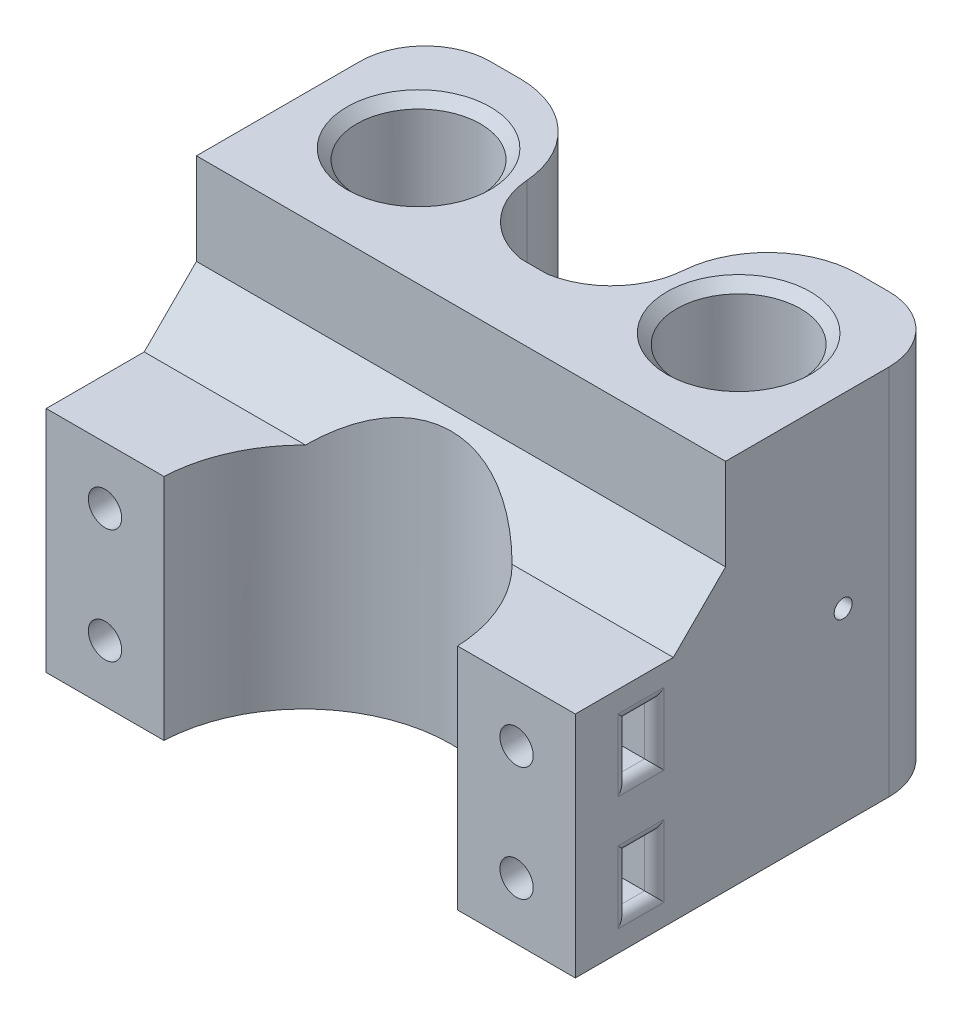
SolidWorks part; units mm, degrees
ref_plane "Alzado" through (0, 0, 0) normal (0, 0, 1) x (1, 0, 0)
ref_plane "Planta" through (0, 0, 0) normal (0, 1, 0) x (1, 0, 0)
ref_plane "Vista lateral" through (0, 0, 0) normal (1, 0, 0) x (0, 0, -1)
sketch "Croquis2" plane through (0, 0, 0) normal (0, 1, 0) x (1, 0, 0)
  line L0 (24.5, 0) -> (-24.5, 0) construction
  line L1 (40.5, 17) -> (-40.5, 17)
  line L2 (-40.5, 17) -> (-40.5, -42)
  line L3 (-40.5, -42) -> (-22.5, -42)
  line L4 (22.5, -42) -> (40.5, -42)
  line L5 (40.5, -42) -> (40.5, 17)
  circle A0 centre (-24.5, 0) radius 9.475
  circle A1 centre (24.5, 0) radius 9.475
  arc A2 (-22.5, -42) -> (22.5, -42) centre (0, -42) cw
  point P4 (0, 0)
  point P10 (0, 17)
  dimension "D1" = 18.95
  dimension "D5" = 22.5
  dimension "D2" = 49
  dimension "D3" = 17
  dimension "D4" = 16
  dimension "D6" = 59
extrude "Saliente-Extruir1" add sketch "Croquis2" along normal blind 35
sketch "Croquis3" plane through (0, 35, 0) normal (0, 1, 0) x (1, 0, 0)
  line L0 (-40.5, 17) -> (-25.923, 17)
  line L1 (40.5, 17) -> (-40.5, 17) construction
  line L3 (40.5, -18) -> (-40.5, -18)
  line L4 (-40.5, 17) -> (-40.5, -42) construction
  line L5 (-40.5, -18) -> (-40.5, 17)
  line L7 (0, 17) -> (0, -19.5) construction
  line L8 (-2, -6.8322) -> (2, -6.8322)
  line L11 (40.5, -18) -> (40.5, 17)
  line L12 (40.5, 17) -> (25.923, 17)
  arc A0 (-25.923, 17) -> (-11.9644, 4.0769) centre (-25.923, 3) cw
  circle A1 centre (0, 5) radius 11 construction
  arc A2 (-11.9644, 4.0769) -> (-2, -6.8322) centre (0, 5) ccw
  arc A4 (22.5, -42) -> (-22.5, -42) centre (0, -42) ccw construction
  circle A8 centre (24.5, 0) radius 9.475
  circle A9 centre (-24.5, 0) radius 9.475 construction
  circle A11 centre (-24.5, 0) radius 9.475
  arc A12 (11.9644, 4.0769) -> (2, -6.8322) centre (0, 5) cw
  arc A13 (25.923, 17) -> (11.9644, 4.0769) centre (25.923, 3) ccw
  point P7 (-24.5, 0)
  point P8 (24.5, 0)
  point P32 (0, -6.8322)
  point P34 (0, -18)
  dimension "D2" = 14
  dimension "D3" = 22
  dimension "D5" = 2
  dimension "D7" = 1
  dimension "D1" = 35
  dimension "D4" = 5
extrude "Saliente-Extruir2" add sketch "Croquis3" along normal blind 22
chamfer "Chaflán1" distance 8 angle 45 1 edges at (0, 35, 18)
fillet "Redondeo3" radius 10 2 edges at (-40.5, 28.5, -17) (40.5, 28.5, -17)
sketch "Croquis4" plane through (0, 57, 0) normal (0, 1, 0) x (1, 0, 0)
  line L2 (-2, -6.8322) -> (2, -6.8322)
  line L3 (25.923, 17) -> (-25.923, 17)
  line L4 (-2, -6.8322) -> (2, -6.8322)
  line L5 (25.923, 17) -> (-25.923, 17)
  arc A4 (-11.9644, 4.0769) -> (-25.923, 17) centre (-25.923, 3) ccw
  arc A5 (-11.9644, 4.0769) -> (-2, -6.8322) centre (0, 5) ccw
  arc A6 (2, -6.8322) -> (11.9644, 4.0769) centre (0, 5) ccw
  arc A7 (25.923, 17) -> (11.9644, 4.0769) centre (25.923, 3) ccw
  arc A8 (-11.9644, 4.0769) -> (-25.923, 17) centre (-25.923, 3) ccw
  arc A9 (-11.9644, 4.0769) -> (-2, -6.8322) centre (0, 5) ccw
  arc A10 (2, -6.8322) -> (11.9644, 4.0769) centre (0, 5) ccw
  arc A11 (25.923, 17) -> (11.9644, 4.0769) centre (25.923, 3) ccw
  dimension "D1" = 0
extrude "Cortar-Extruir1" cut sketch "Croquis4" against normal blind 5 from surface at -22 starting at face at (0, 35, -5.088)
chamfer "Chaflán2" distance 1.5 angle 45 4 edges at (-24.5, 0, 9.475) (24.5, 0, 9.475) (24.5, 57, -9.475) (-24.5, 57, 9.475)
sketch "Croquis5" plane through (0, 30, 0) normal (0, 1, 0) x (1, 0, 0)
  circle A0 centre (0, 5) radius 11 construction
  arc A3 (-11.9644, 4.0769) -> (-2, -6.8322) centre (0, 5) ccw construction
  circle A4 centre (0, 5) radius 5
  circle A5 centre (0, 5) radius 8 construction
  circle A6 centre (0, 13) radius 1.375
  circle A7 centre (8, 5) radius 1.375
  circle A8 centre (0, -3) radius 1.375
  circle A9 centre (-8, 5) radius 1.375
  dimension "D1" = 22
  dimension "D2" = 10
  dimension "D3" = 2.75
  dimension "D4" = 8
extrude "Cortar-Extruir2" cut sketch "Croquis5" against normal through all
chamfer "Chaflán3" distance 0.5 angle 45 10 edges at (8, 0, -3.625) (0, 0, -11.625) (-8, 0, -3.625) (0, 0, 4.375) (0, 30, -11.625) (8, 30, -3.625) (0, 30, 4.375) (-8, 30, -3.625) (0, 0, 0) (0, 30, 0)
sketch "Croquis6" plane through (0, 35, 0) normal (0, 1, 0) x (1, 0, 0)
  line L0 (40.5, -42) -> (40.5, -26) construction
  line L1 (-40.5, -42) -> (40.5, -42)
  line L2 (-40.5, -42) -> (-40.5, -41)
  line L3 (-40.5, -41) -> (40.5, -41)
  line L4 (40.5, -42) -> (40.5, -41)
  dimension "D1" = 1
extrude "Cortar-Extruir3" cut sketch "Croquis6" against normal up to next
sketch "Croquis7" plane through (40.5, 0, 0) normal (1, 0, 0) x (0, 0, -1)
  line L0 (9.475, 28.5) -> (-9.475, 28.5) construction
  line L1 (9.475, 1.5) -> (9.475, 55.5) construction
  line L2 (-9.475, 55.5) -> (-9.475, 1.5) construction
  circle A0 centre (0, 28.5) radius 1.375
  dimension "D1" = 2.75
extrude "Cortar-Extruir4" cut sketch "Croquis7" against normal up to next
mirror "Simetría1" about plane through (0, 0, 0) normal (1, 0, 0) of "Cortar-Extruir4"
sketch "Croquis8" plane through (0, 0, 41) normal (0, 0, 1) x (1, 0, 0)
  circle A0 centre (31.5, 26.25) radius 2.55
  circle A1 centre (31.5, 8.75) radius 2.55
  circle A2 centre (-31.5, 26.25) radius 2.55
  circle A3 centre (-31.5, 8.75) radius 2.55
  dimension "D1" = 5.1
extrude "Cortar-Extruir5" cut sketch "Croquis8" against normal blind 17
sketch "Croquis9" plane through (0, 0, 41) normal (0, 0, 1) x (1, 0, 0)
  line L0 (-22.4778, 35) -> (-40.5, 35) construction
  line L1 (-33.8094, 22.25) -> (-29.1906, 22.25)
  line L2 (-29.1906, 22.25) -> (-26.8812, 26.25)
  line L3 (-26.8812, 26.25) -> (-29.1906, 30.25)
  line L4 (-29.1906, 30.25) -> (-33.8094, 30.25)
  line L5 (-33.8094, 30.25) -> (-36.1188, 26.25) construction
  line L6 (-36.1188, 26.25) -> (-33.8094, 22.25) construction
  line L7 (-36.1188, 8.75) -> (-33.8094, 4.75) construction
  line L8 (-33.8094, 4.75) -> (-29.1906, 4.75)
  line L9 (-29.1906, 4.75) -> (-26.8812, 8.75)
  line L10 (-26.8812, 8.75) -> (-29.1906, 12.75)
  line L11 (-29.1906, 12.75) -> (-33.8094, 12.75)
  line L12 (-33.8094, 12.75) -> (-36.1188, 8.75) construction
  line L25 (-40.5, 22.25) -> (-33.8094, 22.25)
  line L26 (0, 0) -> (0, 41.5) construction
  line L27 (-22.4778, 0) -> (22.4778, 0) construction
  line L28 (-33.8094, 30.25) -> (-40.5, 30.25)
  line L29 (-40.5, 0) -> (-40.5, 35) construction
  line L30 (-40.5, 30.25) -> (-40.5, 22.25)
  line L32 (-33.8094, 12.75) -> (-40.5, 12.75)
  line L33 (-40.5, 12.75) -> (-40.5, 4.75)
  line L34 (-40.5, 4.75) -> (-33.8094, 4.75)
  line L35 (40.5, 12.75) -> (40.5, 4.75)
  line L36 (33.8094, 12.75) -> (40.5, 12.75)
  line L37 (29.1906, 12.75) -> (33.8094, 12.75)
  line L38 (26.8812, 8.75) -> (29.1906, 12.75)
  line L39 (29.1906, 4.75) -> (26.8812, 8.75)
  line L40 (33.8094, 4.75) -> (29.1906, 4.75)
  line L41 (40.5, 4.75) -> (33.8094, 4.75)
  line L42 (40.5, 30.25) -> (40.5, 22.25)
  line L43 (33.8094, 30.25) -> (40.5, 30.25)
  line L44 (29.1906, 30.25) -> (33.8094, 30.25)
  line L45 (26.8812, 26.25) -> (29.1906, 30.25)
  line L46 (29.1906, 22.25) -> (26.8812, 26.25)
  line L47 (33.8094, 22.25) -> (29.1906, 22.25)
  line L48 (40.5, 22.25) -> (33.8094, 22.25)
  circle A0 centre (-31.5, 26.25) radius 4 construction
  circle A1 centre (-31.5, 8.75) radius 4 construction
  arc A2 (15.8193, 35) -> (-15.8193, 35) centre (0, 19) ccw construction
  dimension "D1" = 8
extrude "Cortar-Extruir6" cut sketch "Croquis9" against normal blind 4.1 from offset 8 offset against normal yes
fillet "Redondeo4" radius 1.5 16 edges at (-40.5, 30.25, 30.95) (-40.5, 26.25, 28.9) (-40.5, 22.25, 30.95) (-40.5, 26.25, 33) (-40.5, 8.75, 33) (-40.5, 12.75, 30.95) (-40.5, 8.75, 28.9) (-40.5, 4.75, 30.95) (40.5, 8.75, 28.9) (40.5, 4.75, 30.95) (40.5, 12.75, 30.95) (40.5, 8.75, 33) (40.5, 26.25, 28.9) (40.5, 26.25, 33) (40.5, 30.25, 30.95) (40.5, 22.25, 30.95)
